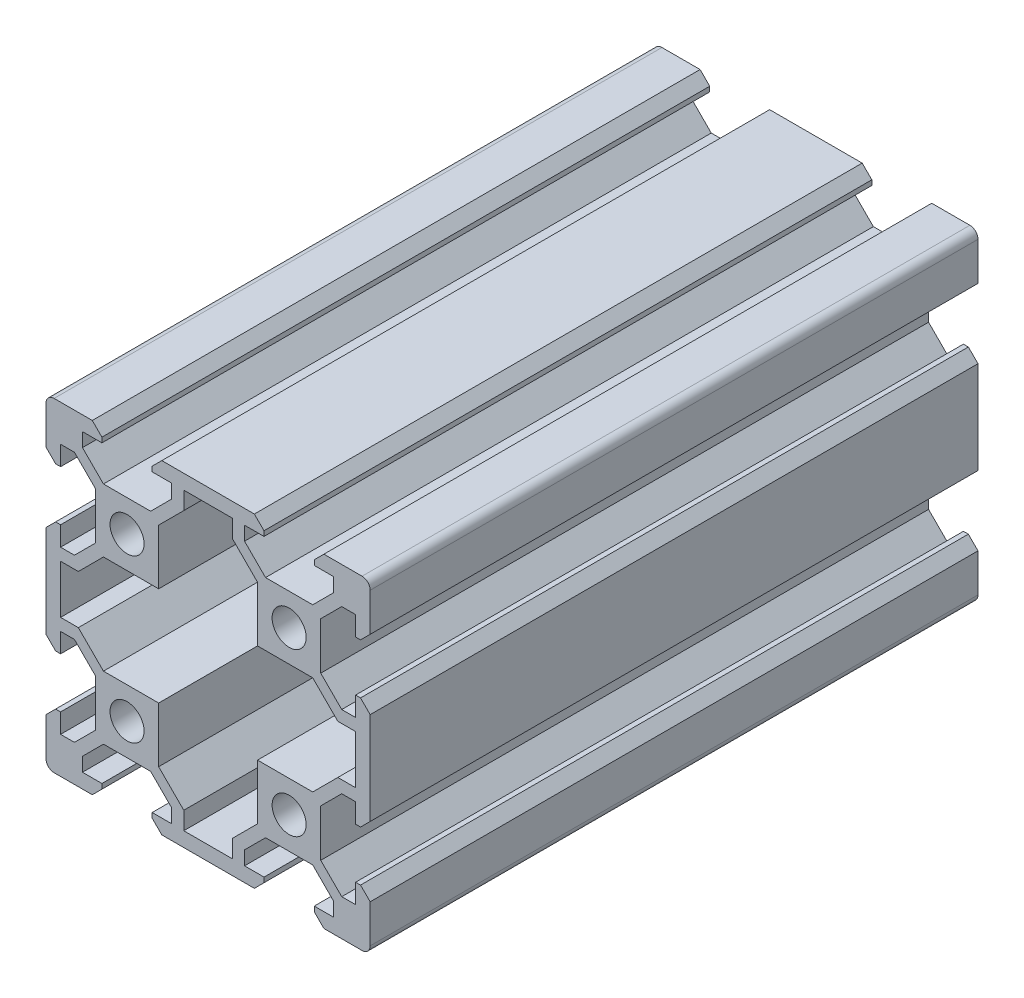
SolidWorks part; units mm, degrees
ref_plane "Front" through (0, 0, 0) normal (0, 0, 1) x (1, 0, 0)
ref_plane "Top" through (0, 0, 0) normal (0, 1, 0) x (1, 0, 0)
ref_plane "Right" through (0, 0, 0) normal (1, 0, 0) x (0, 0, -1)
sketch "草图1" plane through (0, 0, 0) normal (0, 0, 1) x (1, 0, 0)
  line L0 (0, 20) -> (0, -20) construction
  line L1 (-20, -20) -> (20, -20) construction
  line L2 (-20, -20) -> (-20, 20) construction
  line L3 (-20, 20) -> (20, 20) construction
  line L4 (20, -20) -> (20, 20) construction
  line L5 (-20, -20) -> (20, 20) construction
  line L6 (-20, 20) -> (-10, 10) construction
  line L7 (-20, 0) -> (20, 0) construction
  line L8 (5.71, 20) -> (-5.71, 20)
  line L9 (-5.71, 20) -> (-6.9, 18.81)
  line L10 (-6.9, 18.81) -> (-6.9, 18.2)
  line L11 (-6.9, 18.2) -> (-4.5, 18.2)
  line L12 (-4.5, 18.2) -> (-4.5, 16.4899)
  line L13 (-4.5, 16.4899) -> (-7.0899, 13.9)
  line L14 (-7.0899, 13.9) -> (-12.9101, 13.9)
  line L15 (-6.1, 6.1) -> (-6.1, 12.9101)
  line L16 (-6.1, 12.9101) -> (-3, 16.0101)
  line L17 (-3, 16.0101) -> (-3, 18.2)
  line L18 (-3, 18.2) -> (3, 18.2)
  line L19 (-20, 20) -> (-14.29, 20)
  line L20 (-14.29, 20) -> (-13.1, 18.81)
  line L21 (-13.1, 18.81) -> (-13.1, 18.2)
  line L22 (-13.1, 18.2) -> (-15.5, 18.2)
  line L23 (-15.5, 18.2) -> (-15.5, 16.4899)
  line L24 (-15.5, 16.4899) -> (-12.9101, 13.9)
  line L25 (-10, 10) -> (0, 20) construction
  line L26 (-10, 10) -> (-10, 20) construction
  line L27 (-13.9, 6.1) -> (-6.1, 6.1) construction
  line L28 (-13.9, 6.1) -> (-13.9, 13.9) construction
  line L29 (-13.9, 13.9) -> (-6.1, 13.9) construction
  line L30 (-6.1, 6.1) -> (-6.1, 13.9) construction
  line L31 (-13.9, 6.1) -> (-6.1, 13.9) construction
  line L32 (-13.9, 13.9) -> (-10, 10) construction
  line L35 (-10, 10) -> (-6.1, 6.1) construction
  line L37 (-10, 10) -> (20, -20) construction
  line L38 (-16.0101, -3) -> (-18.2, -3)
  line L39 (-20, 20) -> (-20, 14.29)
  line L40 (-20, 14.29) -> (-18.81, 13.1)
  line L41 (-18.81, 13.1) -> (-18.2, 13.1)
  line L42 (-18.2, 13.1) -> (-18.2, 15.5)
  line L43 (-18.2, 15.5) -> (-16.4899, 15.5)
  line L44 (-16.4899, 15.5) -> (-13.9, 12.9101)
  line L45 (-13.9, 7.0899) -> (-13.9, 12.9101)
  line L46 (-16.4899, 4.5) -> (-13.9, 7.0899)
  line L47 (-18.2, 4.5) -> (-16.4899, 4.5)
  line L48 (-18.2, 6.9) -> (-18.2, 4.5)
  line L49 (-18.81, 6.9) -> (-18.2, 6.9)
  line L50 (-20, 5.71) -> (-18.81, 6.9)
  line L51 (-20, -5.71) -> (-20, 5.71)
  line L53 (-18.2, 3) -> (-18.2, -3)
  line L54 (-16.0101, 3) -> (-18.2, 3)
  line L55 (-12.9101, 6.1) -> (-16.0101, 3)
  line L56 (-6.1, 6.1) -> (-12.9101, 6.1)
  line L57 (-12.9101, -6.1) -> (-16.0101, -3)
  line L58 (-6.1, -6.1) -> (-12.9101, -6.1)
  line L59 (-6.1, -6.1) -> (-6.1, -12.9101)
  line L60 (-6.1, -12.9101) -> (-3, -16.0101)
  line L61 (-3, -16.0101) -> (-3, -18.2)
  line L62 (-3, -18.2) -> (3, -18.2)
  line L64 (5.71, -20) -> (-5.71, -20)
  line L65 (-5.71, -20) -> (-6.9, -18.81)
  line L66 (-6.9, -18.81) -> (-6.9, -18.2)
  line L67 (-6.9, -18.2) -> (-4.5, -18.2)
  line L68 (-4.5, -18.2) -> (-4.5, -16.4899)
  line L69 (-4.5, -16.4899) -> (-7.0899, -13.9)
  line L70 (-7.0899, -13.9) -> (-12.9101, -13.9)
  line L71 (-15.5, -16.4899) -> (-12.9101, -13.9)
  line L72 (-15.5, -18.2) -> (-15.5, -16.4899)
  line L73 (-13.1, -18.2) -> (-15.5, -18.2)
  line L74 (-13.1, -18.81) -> (-13.1, -18.2)
  line L75 (-14.29, -20) -> (-13.1, -18.81)
  line L76 (-20, -20) -> (-14.29, -20)
  line L77 (-20, -20) -> (-20, -14.29)
  line L78 (-20, -14.29) -> (-18.81, -13.1)
  line L79 (-18.81, -13.1) -> (-18.2, -13.1)
  line L80 (-18.2, -13.1) -> (-18.2, -15.5)
  line L81 (-18.2, -15.5) -> (-16.4899, -15.5)
  line L82 (-16.4899, -15.5) -> (-13.9, -12.9101)
  line L83 (-13.9, -7.0899) -> (-13.9, -12.9101)
  line L84 (-16.4899, -4.5) -> (-13.9, -7.0899)
  line L85 (-18.2, -4.5) -> (-16.4899, -4.5)
  line L86 (-18.2, -6.9) -> (-18.2, -4.5)
  line L87 (-18.81, -6.9) -> (-18.2, -6.9)
  line L88 (-20, -5.71) -> (-18.81, -6.9)
  line L89 (13.9, 13.9) -> (10, 10) construction
  line L90 (13.9, 6.1) -> (6.1, 13.9) construction
  line L91 (6.1, 6.1) -> (6.1, 13.9) construction
  line L92 (13.9, 13.9) -> (6.1, 13.9) construction
  line L93 (13.9, 6.1) -> (13.9, 13.9) construction
  line L94 (13.9, 6.1) -> (6.1, 6.1) construction
  line L95 (10, 10) -> (10, 20) construction
  line L96 (10, 10) -> (0, 20) construction
  line L97 (20, -5.71) -> (18.81, -6.9)
  line L98 (18.81, -6.9) -> (18.2, -6.9)
  line L99 (18.2, -6.9) -> (18.2, -4.5)
  line L100 (18.2, -4.5) -> (16.4899, -4.5)
  line L101 (16.4899, -4.5) -> (13.9, -7.0899)
  line L102 (13.9, -7.0899) -> (13.9, -12.9101)
  line L103 (16.4899, -15.5) -> (13.9, -12.9101)
  line L104 (18.2, -15.5) -> (16.4899, -15.5)
  line L105 (18.2, -13.1) -> (18.2, -15.5)
  line L106 (18.81, -13.1) -> (18.2, -13.1)
  line L107 (20, -14.29) -> (18.81, -13.1)
  line L108 (20, -20) -> (20, -14.29)
  line L109 (20, -20) -> (14.29, -20)
  line L110 (14.29, -20) -> (13.1, -18.81)
  line L111 (13.1, -18.81) -> (13.1, -18.2)
  line L112 (13.1, -18.2) -> (15.5, -18.2)
  line L113 (15.5, -18.2) -> (15.5, -16.4899)
  line L114 (15.5, -16.4899) -> (12.9101, -13.9)
  line L115 (7.0899, -13.9) -> (12.9101, -13.9)
  line L116 (4.5, -16.4899) -> (7.0899, -13.9)
  line L117 (4.5, -18.2) -> (4.5, -16.4899)
  line L118 (6.9, -18.2) -> (4.5, -18.2)
  line L119 (6.9, -18.81) -> (6.9, -18.2)
  line L120 (5.71, -20) -> (6.9, -18.81)
  line L121 (3, -16.0101) -> (3, -18.2)
  line L122 (6.1, -12.9101) -> (3, -16.0101)
  line L123 (6.1, -6.1) -> (6.1, -12.9101)
  line L124 (6.1, -6.1) -> (12.9101, -6.1)
  line L125 (12.9101, -6.1) -> (16.0101, -3)
  line L126 (6.1, 6.1) -> (12.9101, 6.1)
  line L127 (12.9101, 6.1) -> (16.0101, 3)
  line L128 (16.0101, 3) -> (18.2, 3)
  line L129 (18.2, 3) -> (18.2, -3)
  line L130 (20, -5.71) -> (20, 5.71)
  line L131 (20, 5.71) -> (18.81, 6.9)
  line L132 (18.81, 6.9) -> (18.2, 6.9)
  line L133 (18.2, 6.9) -> (18.2, 4.5)
  line L134 (18.2, 4.5) -> (16.4899, 4.5)
  line L135 (16.4899, 4.5) -> (13.9, 7.0899)
  line L136 (13.9, 7.0899) -> (13.9, 12.9101)
  line L137 (16.4899, 15.5) -> (13.9, 12.9101)
  line L138 (18.2, 15.5) -> (16.4899, 15.5)
  line L139 (18.2, 13.1) -> (18.2, 15.5)
  line L140 (18.81, 13.1) -> (18.2, 13.1)
  line L141 (20, 14.29) -> (18.81, 13.1)
  line L142 (20, 20) -> (20, 14.29)
  line L143 (16.0101, -3) -> (18.2, -3)
  line L144 (15.5, 16.4899) -> (12.9101, 13.9)
  line L145 (15.5, 18.2) -> (15.5, 16.4899)
  line L146 (13.1, 18.2) -> (15.5, 18.2)
  line L147 (13.1, 18.81) -> (13.1, 18.2)
  line L148 (14.29, 20) -> (13.1, 18.81)
  line L149 (20, 20) -> (14.29, 20)
  line L150 (3, 16.0101) -> (3, 18.2)
  line L151 (6.1, 12.9101) -> (3, 16.0101)
  line L152 (6.1, 6.1) -> (6.1, 12.9101)
  line L153 (7.0899, 13.9) -> (12.9101, 13.9)
  line L154 (4.5, 16.4899) -> (7.0899, 13.9)
  line L155 (4.5, 18.2) -> (4.5, 16.4899)
  line L156 (6.9, 18.2) -> (4.5, 18.2)
  line L157 (6.9, 18.81) -> (6.9, 18.2)
  line L158 (5.71, 20) -> (6.9, 18.81)
  circle A0 centre (-10, 10) radius 2.1
  circle A1 centre (-10, -10) radius 2.1
  circle A2 centre (10, -10) radius 2.1
  circle A3 centre (10, 10) radius 2.1
  point P0 (0, 0)
  point P59 (-18.2, 0)
  point P124 (0, -18.2)
  point P152 (0, 18.2)
  dimension "D10" = 4.2
  dimension "D1" = 40
  dimension "D2" = 6
  dimension "D3" = 1.8
  dimension "D4" = 45
  dimension "D5" = 4.5
  dimension "D6" = 45
  dimension "D7" = 6.2
  dimension "D8" = 0.61
  dimension "D9" = 1.4
  dimension "D12" = 7.8
  dimension "D13" = 1.5
  dimension "D14" = 1.4
  dimension "D15" = 7.8
extrude "凸台-拉伸1" add sketch "草图1" along normal blind 75
ref_plane "Ebene1" through (0, 0, 0) normal (-0.7071, -0.7071, 0) x (-0.7071, 0.7071, 0)
fillet "Verrundung1" radius 1 4 edges at (20, -20, 37.5) (-20, -20, 37.5) (-20, 20, 37.5) (20, 20, 37.5)
ref_plane "Plane1" through (0, 0, 0) normal (-0.7071, 0.7071, 0) x (0.7071, 0.7071, 0)
